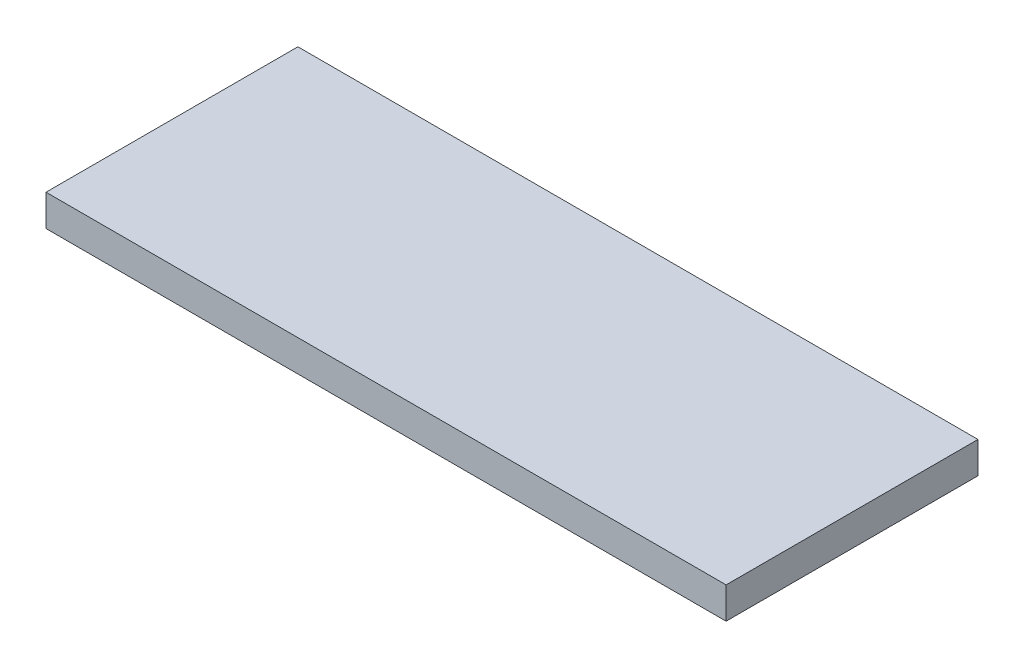
SolidWorks part; units mm, degrees
ref_plane "Front Plane" through (0, 0, 0) normal (0, 0, 1) x (1, 0, 0)
ref_plane "Top Plane" through (0, 0, 0) normal (0, 1, 0) x (1, 0, 0)
ref_plane "Right Plane" through (0, 0, 0) normal (1, 0, 0) x (0, 0, -1)
sketch "Sketch1" plane through (0, 0, 0) normal (0, 1, 0) x (1, 0, 0)
  line L1 (0, 0) -> (68.58, 0)
  line L2 (0, 0) -> (0, 25.4)
  line L3 (0, 25.4) -> (68.58, 25.4)
  line L4 (68.58, 0) -> (68.58, 25.4)
  dimension "D1" = 25.4
  dimension "D2" = 68.58
extrude "Boss-Extrude1" add sketch "Sketch1" along normal blind 3.175
